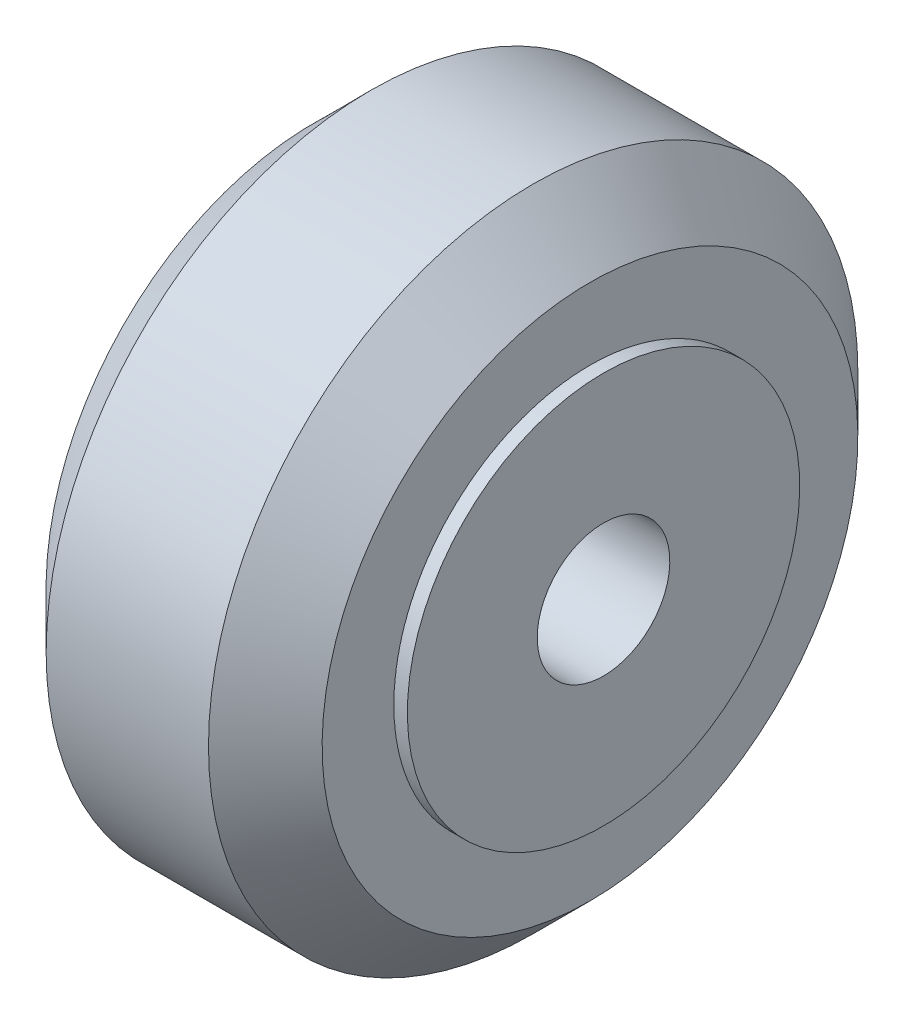
SolidWorks part; units mm, degrees
ref_plane "Alzado" through (0, 0, 0) normal (0, 0, 1) x (1, 0, 0)
ref_plane "Planta" through (0, 0, 0) normal (0, 1, 0) x (1, 0, 0)
ref_plane "Vista lateral" through (0, 0, 0) normal (1, 0, 0) x (0, 0, -1)
sketch "Croquis1" plane through (0, 0, 0) normal (0, 0, 1) x (1, 0, 0)
  line L0 (0, 0) -> (-3, 0) construction
  line L1 (-3, 0) -> (-3, 2.45) construction
  line L2 (-3, 12) -> (3, 12)
  line L5 (0, 12) -> (0, 0) construction
  line L6 (-3, 12) -> (-5.1, 9.9)
  line L10 (-3, 0) -> (-3, 2.45) construction
  line L11 (0, 0) -> (-3, 2.45) construction
  line L12 (3, 2.45) -> (5.1, 2.45)
  line L13 (0, 0) -> (-5.1, 0) construction
  line L14 (-5.1, 0) -> (-5.1, 9.9)
  line L15 (-3, 2.45) -> (3, 2.45)
  line L16 (-3, 2.45) -> (-5.1, 2.45)
  line L17 (5.1, 0) -> (5.1, 9.9)
  line L18 (3, 12) -> (5.1, 9.9)
  line L19 (0, 0) -> (5.1, 0) construction
  point P6 (0, 2.45)
  dimension "D2" = 12
  dimension "D3" = 45
  dimension "D4" = 9.9
revolve "Revolución1" add sketch "Croquis1" angle 360 about L19 region at (0, 7.0318, 0)
sketch "Croquis2" plane through (5.1, 0, 0) normal (1, 0, 0) x (0, 0, -1)
  circle A0 centre (0, 0) radius 7.25
  circle A1 centre (0, 0) radius 2.45
  dimension "D1" = 14.5
extrude "Saliente-Extruir1" add sketch "Croquis2" along normal blind 0.5 and the other way blind 10.6 separate body contours A0 | A1
sketch "Croquis3" plane through (5.1, 0, 0) normal (1, 0, 0) x (0, 0, -1)
  circle A0 centre (0, 0) radius 7.25
extrude "Cortar-Extruir1" cut sketch "Croquis3" against normal blind 17.5 and the other way blind 14
